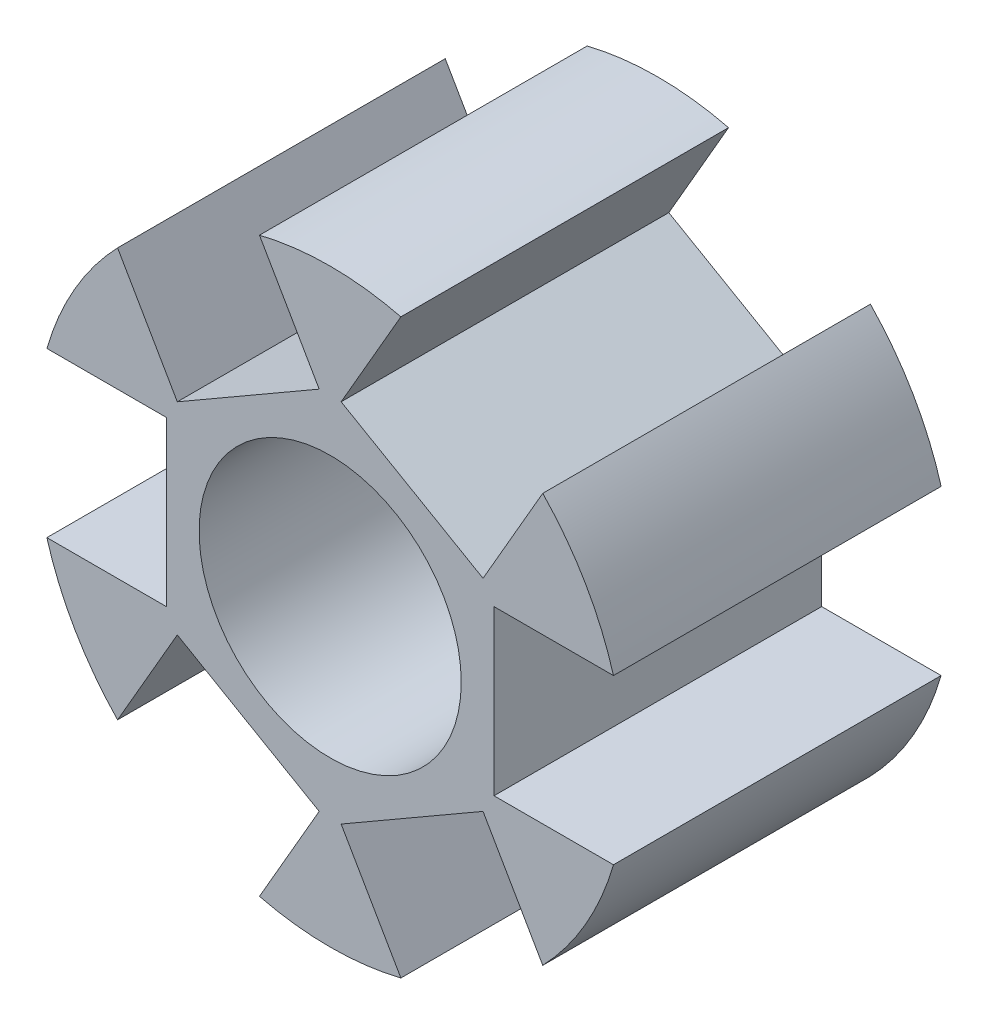
SolidWorks part; units mm, degrees
ref_plane "Top Plane" through (0, 0, 0) normal (0, 0, 1) x (1, 0, 0)
ref_plane "Right Plane" through (0, 0, 0) normal (0, 1, 0) x (1, 0, 0)
ref_plane "Front Plane" through (0, 0, 0) normal (1, 0, 0) x (0, 0, -1)
ref_axis "x-axis" through (-88.99, 0, 0) along (1, 0, 0)
ref_axis "y-axis" through (0, -55, 0) along (0, 1, 0)
ref_axis "z-axis" through (0, 0, 55) along (0, 0, -1)
sketch "Sketch1" plane through (0, 0, 0) normal (0, 0, 1) x (1, 0, 0)
  line L8 (-19.9785, 0) -> (0, 0) construction
  line L16 (0, 0) -> (0, -20.7846) construction
  line L23 (0, 0) -> (0, -20.7846) construction
  circle A0 centre (0, 0) radius 4
  circle A3 centre (0, 0) radius 9
  dimension "D1" = 8
  dimension "D2" = 18
extrude "Boss-Extrude1" add sketch "Sketch1" along normal mid plane 10
ref_plane "Plane1" through (-9, 0, 0) normal (-1, 0, 0) x (0, 0, 1)
sketch "Sketch2" plane through (-9, -17.1931, 0) normal (1, 0, 0) x (0, -1, 0)
  line L1 (-19.6931, -5) -> (-14.6931, -5)
  line L2 (-19.6931, -5) -> (-19.6931, 5)
  line L3 (-19.6931, 5) -> (-14.6931, 5)
  line L4 (-14.6931, -5) -> (-14.6931, 5)
  line L5 (-19.6931, -5) -> (-14.6931, 5) construction
  line L6 (-19.6931, 5) -> (-14.6931, -5) construction
  point P0 (-17.1931, 0)
  dimension "D1" = 5
  dimension "D2" = 10
extrude "Cut-Extrude3" cut sketch "Sketch2" along normal blind 4
pattern_circular "CirPattern1" count 6 over 360 about axis through (0, 0, 5) along (0, 0, 1) of "Cut-Extrude3"
